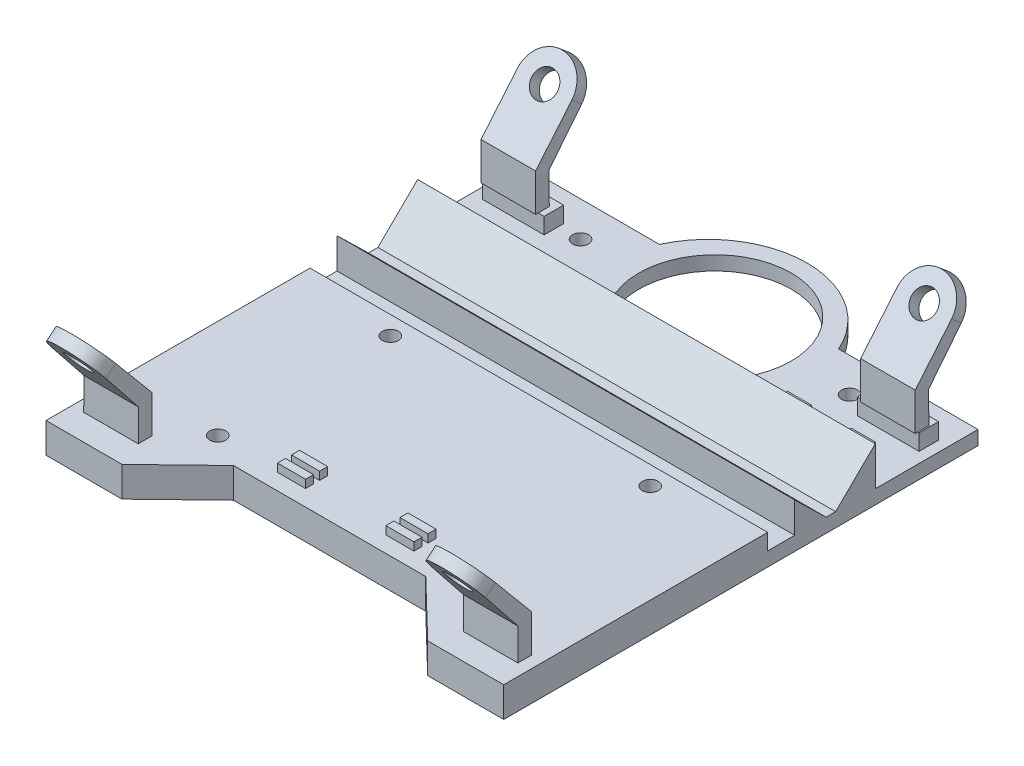
SolidWorks part; units mm, degrees
ref_plane "Ebene vorne" through (0, 0, 0) normal (0, 0, 1) x (1, 0, 0)
ref_plane "Ebene oben" through (0, 0, 0) normal (0, 1, 0) x (1, 0, 0)
ref_plane "Ebene rechts" through (0, 0, 0) normal (1, 0, 0) x (0, 0, -1)
sketch "Skizze1" plane through (0, 0, 0) normal (0, 1, 0) x (1, 0, 0)
  line L1 (0, 0) -> (57, 0)
  line L2 (0, 0) -> (0, 60)
  line L3 (0, 60) -> (57, 60)
  line L4 (57, 0) -> (57, 60)
  dimension "D1" = 57
  dimension "D2" = 60
extrude "Aufsatz-Linear austragen1" add sketch "Skizze1" against normal blind 1.75
sketch "Skizze3" plane through (0, 0, 0) normal (0, 1, 0) x (1, 0, 0)
  line L0 (57, 60) -> (0, 60) construction
  line L2 (57, 0) -> (57, 60) construction
  circle A0 centre (28.5, 48) radius 9.4954
  dimension "D1" = 12
  dimension "D2" = 28.5
extrude "Schnitt-Linear austragen1" cut sketch "Skizze3" against normal blind 2
sketch "Skizze4" plane through (0, 0, 0) normal (0, 1, 0) x (1, 0, 0)
  line L0 (0, 60) -> (0, 0) construction
  line L1 (57, 0) -> (0, 0)
  line L2 (57, 0) -> (57, 26.0545)
  line L3 (57, 26.0545) -> (0, 26.0545)
  line L4 (0, 0) -> (0, 26.0545)
extrude "Aufsatz-Linear austragen2" add sketch "Skizze4" along normal blind 2
sketch "Skizze5" plane through (0, 2, 0) normal (0, 1, 0) x (1, 0, 0)
  circle A0 centre (12.3153, 23.7449) radius 1
  circle A1 centre (12.3153, 2.2449) radius 1
  dimension "D1" = 2
  dimension "D2" = 2
extrude "Schnitt-Linear austragen2" cut sketch "Skizze5" against normal blind 4
ref_plane "Ebene1" through (28.5, 0, 0) normal (-1, 0, 0) x (0, 0, 1)
mirror "Spiegeln1" about plane through (28.5, 0, 0) normal (-1, 0, 0) of "Schnitt-Linear austragen2"
sketch "Skizze8" plane through (0, 0, 0) normal (-1, 0, 0) x (0, 0, 1)
  line L1 (-29.4199, 3.8153) -> (-33.3253, 0)
  line L4 (-60, 0) -> (-26.0545, 0) construction
  line L8 (-33.3253, 0) -> (-29.4199, 0)
  line L10 (-29.4199, 0) -> (-29.4199, 3.8153)
extrude "Aufsatz-Linear austragen3" add sketch "Skizze8" against normal blind 57
sketch "Skizze10" plane through (0, 0, 0) normal (0, 1, 0) x (1, 0, 0)
  line L1 (57, 60) -> (0, 60) construction
  line L2 (57, 33.3253) -> (57, 60) construction
  line L3 (0, 60) -> (0, 33.3253) construction
  circle A0 centre (45.25, 48) radius 1
  circle A1 centre (11.75, 48) radius 1
  dimension "D1" = 12
  dimension "D2" = 12
  dimension "D3" = 11.75
  dimension "D4" = 11.75
extrude "Schnitt-Linear austragen3" cut sketch "Skizze10" against normal blind 2
sketch "Skizze11" plane through (0, 0, 0) normal (-1, 0, 0) x (0, 0, 1)
  line L0 (-39.4583, 4.8503) -> (-39.4583, 0)
  line L1 (-60, 0) -> (-33.3253, 0) construction
  line L2 (-39.4583, 0) -> (-34.5117, 0)
  line L3 (-34.5117, 0) -> (-39.4583, 4.8503)
extrude "Aufsatz-Linear austragen4" add sketch "Skizze11" against normal blind 57
sketch "Skizze13" plane through (0, 0, 0) normal (0, 1, 0) x (1, 0, 0)
  line L0 (53, 42.5) -> (50, 42.5)
  line L1 (50, 42.5) -> (50, 43.5)
  line L2 (50, 43.5) -> (53, 43.5)
  line L5 (45, 42.5) -> (45, 43.5)
  line L6 (45, 43.5) -> (42, 43.5)
  line L7 (42, 43.5) -> (42, 42.5)
  line L8 (42, 42.5) -> (45, 42.5)
  line L9 (53, 40.75) -> (50, 40.75)
  line L10 (50, 40.75) -> (50, 41.75)
  line L11 (50, 41.75) -> (53, 41.75)
  line L12 (53, 41.75) -> (53, 40.75)
  line L14 (45, 41.75) -> (42, 41.75)
  line L15 (42, 41.75) -> (42, 40.75)
  line L16 (42, 40.75) -> (45, 40.75)
  line L17 (45, 40.75) -> (45, 41.75)
  line L18 (57, 60) -> (0, 60) construction
  line L19 (57, 39.4583) -> (57, 60) construction
  line L20 (53, 42.5) -> (53, 43.5)
  dimension "D1" = 0.75
  dimension "D2" = 1
  dimension "D3" = 1
  dimension "D4" = 0.75
  dimension "D5" = 16.5
  dimension "D6" = 16.5
  dimension "D7" = 4
  dimension "D8" = 1
  dimension "D9" = 3
  dimension "D10" = 1
  dimension "D11" = 3
  dimension "D12" = 3
  dimension "D13" = 16.5
extrude "Aufsatz-Linear austragen6" add sketch "Skizze13" along normal blind 1
sketch "Skizze16" plane through (0, 2, 0) normal (0, 1, 0) x (1, 0, 0)
  line L5 (20, 2) -> (23.5, 2)
  line L6 (20, 2) -> (20, 3)
  line L7 (20, 3) -> (23.5, 3)
  line L8 (23.5, 2) -> (23.5, 3)
  line L9 (33.5, 2) -> (37, 2)
  line L11 (33.5, 2) -> (33.5, 3)
  line L12 (33.5, 3) -> (37, 3)
  line L13 (37, 2) -> (37, 3)
  line L14 (20, 3.75) -> (23.5, 3.75)
  line L15 (20, 3.75) -> (20, 4.75)
  line L16 (20, 4.75) -> (23.5, 4.75)
  line L17 (23.5, 3.75) -> (23.5, 4.75)
  line L18 (33.5, 3.75) -> (37, 3.75)
  line L19 (33.5, 3.75) -> (33.5, 4.75)
  line L20 (33.5, 4.75) -> (37, 4.75)
  line L21 (37, 3.75) -> (37, 4.75)
  line L22 (0, 0) -> (57, 0) construction
  line L23 (0, 0) -> (57, 0) construction
  line L24 (0, 26.0545) -> (0, 0) construction
  point P20 (23.5, 2.5)
  dimension "D1" = 1
  dimension "D2" = 1
  dimension "D3" = 1
  dimension "D4" = 1
  dimension "D5" = 3.5
  dimension "D6" = 3.5
  dimension "D7" = 3.5
  dimension "D8" = 3.5
  dimension "D9" = 0.75
  dimension "D10" = 0.75
  dimension "D11" = 2
  dimension "D12" = 2
  dimension "D13" = 10
  dimension "D14" = 0
  dimension "D15" = 20
extrude "Aufsatz-Linear austragen9" add sketch "Skizze16" along normal blind 1
sketch "Skizze20" plane through (57, 0, 0) normal (1, 0, 0) x (0, 0, -1)
  line L0 (0, 2) -> (0, 7.048)
  line L1 (0, 2) -> (26.0545, 2) construction
  line L2 (0, 7.048) -> (4, 7.048)
  line L3 (4, 7.048) -> (4, 2)
  line L4 (4, 2) -> (4, 21.5) construction
  line L5 (4, 2) -> (0, 2)
  dimension "D1" = 4
  dimension "D2" = 4
sketch "Skizze24" plane through (0, 2, 0) normal (0, 1, 0) x (1, 0, 0)
  line L0 (57, 0) -> (57, -15.9632)
  line L1 (57, -15.9632) -> (46.4704, -5.7952)
  line L2 (46.4704, -5.7952) -> (40.4691, 0)
  line L3 (0, 0) -> (57, 0) construction
  line L6 (40.4691, 0) -> (57, 0)
extrude "Aufsatz-Linear austragen11" add sketch "Skizze24" against normal blind 3.75
mirror "Spiegeln2" about plane through (28.5, 0, 0) normal (-1, 0, 0) of "Aufsatz-Linear austragen11"
sketch "Skizze25" plane through (0, 2, 0) normal (0, 1, 0) x (1, 0, 0)
  line L14 (48.7359, -1.2853) -> (55.5359, -1.2853)
  line L15 (48.7359, -1.2853) -> (48.7359, -5.9633)
  line L16 (48.7359, -5.9633) -> (55.5359, -5.9633)
  line L17 (55.5359, -1.2853) -> (55.5359, -5.9633)
  dimension "D1" = 6.8
extrude "Aufsatz-Linear austragen12" add sketch "Skizze25" along normal blind 13
sketch "Skizze26" plane through (55.5359, 0, 0) normal (1, 0, 0) x (0, 0, -1)
  line L0 (-5.9633, 7.8681) -> (-12.2355, 7.8681)
  line L1 (-5.9633, 15) -> (-5.9633, 2) construction
  line L2 (-12.2355, 7.8681) -> (-12.2355, 15)
  line L3 (-12.2355, 15) -> (-5.9633, 15)
  line L4 (-5.9633, 15) -> (-5.9633, 7.8681)
extrude "Aufsatz-Linear austragen13" add sketch "Skizze26" against normal blind 6.8
sketch "Skizze27" plane through (55.5359, 0, 0) normal (1, 0, 0) x (0, 0, -1)
  line L0 (-12.2355, 15) -> (-1.2853, 15) construction
  line L1 (-10.7685, 15) -> (-3.5522, 5.947)
  line L2 (-3.5522, 5.947) -> (-3.5907, 2)
  line L3 (-15.9632, 2) -> (26.0545, 2) construction
  line L4 (-3.5907, 2) -> (-6.081, 2)
  line L5 (-6.081, 2) -> (-5.9633, 7.8681)
  line L6 (-5.9633, 7.8681) -> (-12.2355, 7.8681)
  line L7 (-12.2355, 7.8681) -> (-12.2355, 15)
  line L8 (-12.2355, 15) -> (-10.7685, 15)
  circle A0 centre (12.9949, 7) radius 17.3229 construction
extrude "Schnitt-Linear austragen5" cut sketch "Skizze27" against normal blind 6.8
sketch "Skizze28" plane through (55.5359, 0, 0) normal (1, 0, 0) x (0, 0, -1)
  line L0 (-9.8552, 13.8542) -> (-8.6758, 14.7943)
  line L1 (-3.5522, 5.947) -> (-10.7685, 15) construction
  line L2 (-8.6758, 14.7943) -> (-1.8918, 6.6863)
  line L3 (-1.8918, 6.6863) -> (-1.8918, 2)
  line L4 (-15.9632, 2) -> (26.0545, 2) construction
  line L5 (-1.8918, 2) -> (-1.2415, 2)
  line L6 (-1.2415, 2) -> (-1.2415, 15.4301)
  line L7 (-1.2415, 15.4301) -> (-11.1128, 15.4301)
  line L8 (-11.1128, 15.4301) -> (-9.8552, 13.8542)
extrude "Schnitt-Linear austragen6" cut sketch "Skizze28" against normal blind 6.8 contours L2 L3 L5 L6 L7 L8 L0
sketch "Skizze29" plane through (0, 1.8223, -2.178) normal (0, 0.6417, -0.7669) x (-1, 0, 0)
  line L8 (-55.5359, 13.3838) -> (-55.5359, 17.0838)
  line L9 (-55.5359, 16.9138) -> (-55.5359, 6.342) construction
  line L10 (-55.5359, 17.0838) -> (-48.7359, 17.0838)
  line L11 (-48.7359, 17.0838) -> (-48.7359, 13.3838)
  line L12 (-48.7359, 16.9138) -> (-48.7359, 6.342) construction
  arc A1 (-48.7359, 13.3838) -> (-55.5359, 13.3838) centre (-52.1359, 13.3838) ccw
  dimension "D1" = 3.4
  dimension "D2" = 3.7
  dimension "D3" = 3.53
extrude "Schnitt-Linear austragen8" cut sketch "Skizze29" against normal blind 3.8
sketch "Skizze30" plane through (0, 1.8223, -2.178) normal (0, 0.6417, -0.7669) x (-1, 0, 0)
  circle A0 centre (-52.1359, 13.3838) radius 1.6
  arc A1 (-48.7359, 13.3838) -> (-55.5359, 13.3838) centre (-52.1359, 13.3838) ccw construction
  dimension "D1" = 3.2
  dimension "D2" = 0
extrude "Schnitt-Linear austragen9" cut sketch "Skizze30" against normal blind 3.8
mirror "Spiegeln6" about plane through (28.5, 0, 0) normal (-1, 0, 0) of "Schnitt-Linear austragen9", "Schnitt-Linear austragen8", "Schnitt-Linear austragen6", "Schnitt-Linear austragen5", "Aufsatz-Linear austragen13", "Aufsatz-Linear austragen12"
ref_plane "Ebene2" through (0, 0, -22) normal (0, 0, -1) x (-1, 0, 0)
sketch "Skizze31" plane through (0, 0, 0) normal (0, 1, 0) x (1, 0, 0)
  line L1 (48, 46.2086) -> (55.6975, 46.2086)
  line L2 (48, 46.2086) -> (48, 48.6381)
  line L3 (48, 48.6381) -> (55.6975, 48.6381)
  line L4 (55.6975, 46.2086) -> (55.6975, 48.6381)
extrude "Aufsatz-Linear austragen15" add sketch "Skizze31" along normal blind 2
mirror "Spiegeln8" about plane through (0, 0, -22) normal (0, 0, -1) of "Schnitt-Linear austragen9", "Schnitt-Linear austragen8", "Schnitt-Linear austragen6", "Schnitt-Linear austragen5", "Aufsatz-Linear austragen13", "Aufsatz-Linear austragen12"
mirror "Spiegeln9" about plane through (28.5, 0, 0) normal (-1, 0, 0) of "Spiegeln8", "Aufsatz-Linear austragen15"
sketch "Skizze36" plane through (0, 0, 0) normal (0, 1, 0) x (1, 0, 0)
  line L0 (0, 52.369) -> (17.2084, 52.369)
  line L1 (57, 52.2455) -> (57, 60)
  line L2 (57, 60) -> (0, 60)
  line L3 (0, 60) -> (0, 52.369)
  line L4 (57, 52.2455) -> (39.6409, 52.2455)
  arc A0 (17.2084, 52.369) -> (39.6409, 52.2455) centre (28.3968, 47.2564) cw
extrude "Schnitt-Linear austragen10" cut sketch "Skizze36" against normal blind 10 contours L4 A0 L0 L3 L2 L1
sketch "Skizze37" plane through (0, 2, 0) normal (0, 1, 0) x (1, 0, 0)
  line L0 (0, -6.8214) -> (9.5761, -6.8214)
  line L1 (9.5761, -6.8214) -> (0, -15.9632)
  line L2 (0, -15.9632) -> (0, -6.8214)
extrude "Schnitt-Linear austragen11" cut sketch "Skizze37" against normal blind 10
mirror "Spiegeln10" about plane through (28.5, 0, 0) normal (-1, 0, 0) of "Schnitt-Linear austragen11"
ref_plane "Ebene14" through (0, 0.4646, -47.6057) normal (0, 0.0098, -1) x (-1, 0, 0)
